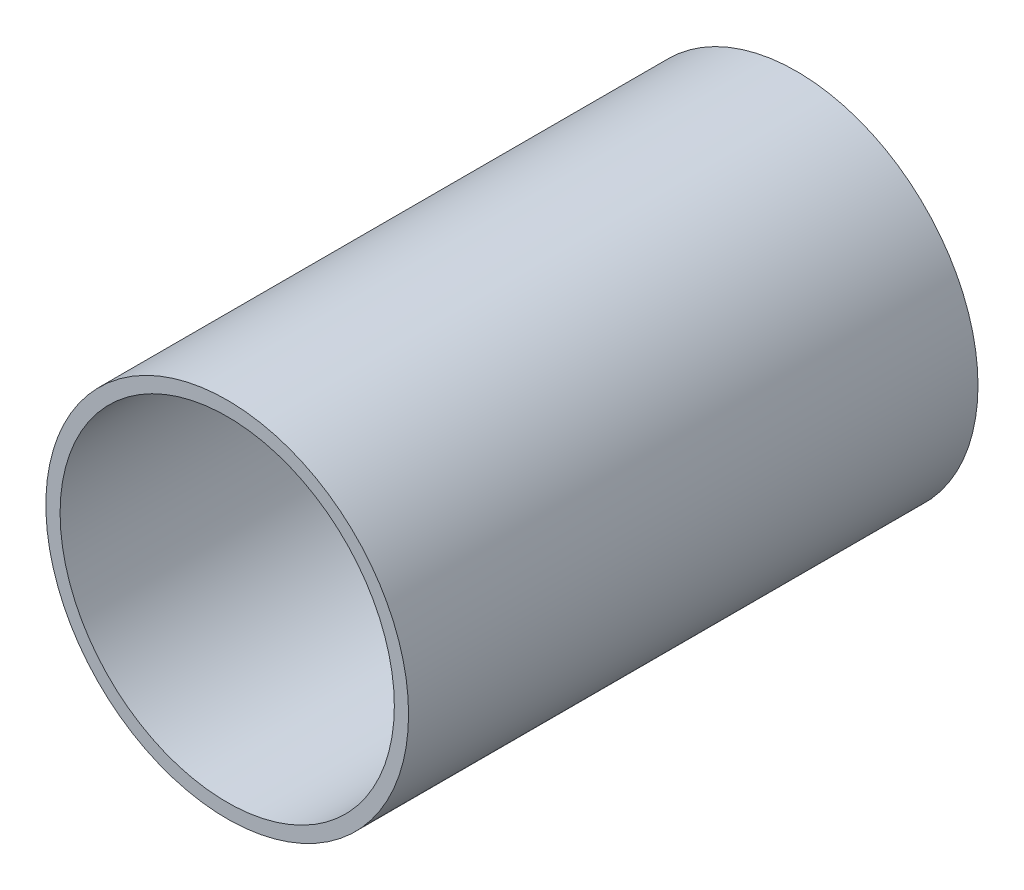
SolidWorks part; units mm, degrees
ref_plane "Front Plane" through (0, 0, 0) normal (0, 0, 1) x (1, 0, 0)
ref_plane "Top Plane" through (0, 0, 0) normal (0, 1, 0) x (1, 0, 0)
ref_plane "Right Plane" through (0, 0, 0) normal (1, 0, 0) x (0, 0, -1)
sketch "Sketch1" plane through (0, 0, 0) normal (0, 0, 1) x (1, 0, 0)
  circle A0 centre (0, 0) radius 2.935
  circle A1 centre (0, 0) radius 3.185
  circle A2 centre (0, 0) radius 2.935
  dimension "D1" = 6.37
  dimension "D2" = 5.87
extrude "Boss-Extrude2" add sketch "Sketch1" along normal blind 10 contours A1 | A0
extrude "Boss-Extrude3" add sketch "Sketch1<6>" along normal blind 0.5 contours A0
sketch "Sketch1<6>" plane through (0, 0, 0) normal (0, 0, 1) x (1, 0, 0) same geometry as "Sketch1"
